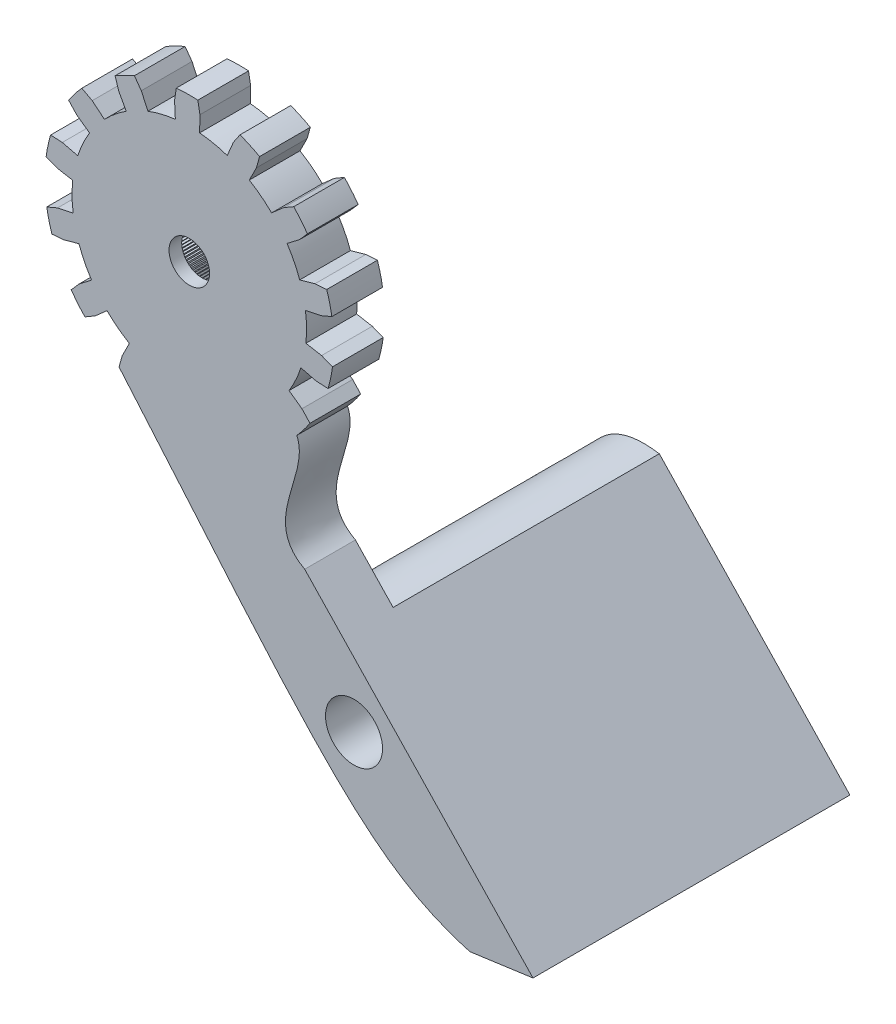
SolidWorks part; units mm, degrees
ref_plane "Front Plane" through (0, 0, 0) normal (0, 0, 1) x (1, 0, 0)
ref_plane "Top Plane" through (0, 0, 0) normal (0, 1, 0) x (1, 0, 0)
ref_plane "Right Plane" through (0, 0, 0) normal (1, 0, 0) x (0, 0, -1)
sketch "Sketch2" plane through (0, 0, 0) normal (0, 0, 1) x (1, 0, 0)
  line L0 (11.1946, 10) -> (11.1946, 10.6054) construction
  line L669 (17.6878, 7.31) -> (18.6279, 8.138)
  line L670 (18.6279, 8.138) -> (19.4304, 8.6044)
  line L671 (21.6272, -0.4657) -> (22.4922, -0.8024)
  line L672 (20.3937, -0.247) -> (21.6272, -0.4657)
  line L673 (20.3589, 1.9784) -> (21.5849, 2.2356)
  line L674 (21.5849, 2.2356) -> (22.439, 2.5991)
  line L675 (21.1094, 4.1784) -> (22.0348, 4.2505)
  line L676 (19.9032, 3.8403) -> (21.1094, 4.1784)
  line L677 (18.9062, 5.8303) -> (19.8993, 6.5939)
  line L678 (19.8993, 6.5939) -> (20.511, 7.292)
  line L679 (14.4587, -7.9329) -> (14.9822, -9.071)
  line L680 (14.9822, -9.071) -> (15.5266, -9.8227)
  line L681 (16.7705, -8.175) -> (17.0467, -9.0612)
  line L682 (16.1724, -7.0743) -> (16.7705, -8.175)
  line L683 (17.8907, -5.6595) -> (18.8561, -6.4578)
  line L684 (18.8561, -6.4578) -> (19.6729, -6.8988)
  line L685 (20.0786, -4.8746) -> (20.7119, -5.5532)
  line L686 (19.0622, -4.1424) -> (20.0786, -4.8746)
  line L687 (19.9964, -2.1222) -> (21.2126, -2.4225)
  line L688 (21.2126, -2.4225) -> (22.1398, -2.4655)
  line L689 (3.4829, -4.3861) -> (2.4899, -5.1497)
  line L690 (2.4899, -5.1497) -> (1.8781, -5.8478)
  line L691 (3.7613, -6.6939) -> (2.9588, -7.1603)
  line L692 (4.7013, -5.8658) -> (3.7613, -6.6939)
  line L693 (6.463, -7.2262) -> (5.8996, -8.3451)
  line L694 (5.8996, -8.3451) -> (5.6513, -9.2394)
  line L695 (7.7151, -9.1846) -> (7.1944, -9.953)
  line L696 (8.2027, -8.0307) -> (7.7151, -9.1846)
  line L697 (10.3802, -8.492) -> (10.3581, -9.7445)
  line L698 (10.3581, -9.7445) -> (10.5224, -10.6581)
  line L699 (12.358, -9.7133) -> (12.2223, -10.6315)
  line L700 (12.2967, -8.462) -> (12.358, -9.7133)
  line L701 (2.3105, 6.3188) -> (1.6772, 6.9974)
  line L702 (3.327, 5.5866) -> (2.3105, 6.3188)
  line L703 (2.3927, 3.5664) -> (1.1765, 3.8667)
  line L704 (1.1765, 3.8667) -> (0.2493, 3.9097)
  line L705 (0.762, 1.9099) -> (-0.103, 2.2465)
  line L706 (1.9955, 1.6912) -> (0.762, 1.9099)
  line L707 (2.0303, -0.5343) -> (0.8042, -0.7914)
  line L708 (0.8042, -0.7914) -> (-0.0498, -1.1549)
  line L709 (1.2798, -2.7343) -> (0.3543, -2.8063)
  line L710 (2.486, -2.3961) -> (1.2798, -2.7343)
  line L711 (12.009, 9.9362) -> (12.0311, 11.1887)
  line L712 (12.0311, 11.1887) -> (11.8667, 12.1023)
  line L713 (10.0311, 11.1574) -> (10.1668, 12.0757)
  line L714 (10.0924, 9.9062) -> (10.0311, 11.1574)
  line L715 (7.9305, 9.377) -> (7.4069, 10.5151)
  line L716 (7.4069, 10.5151) -> (6.8625, 11.2669)
  line L717 (5.6186, 9.6192) -> (5.3425, 10.5054)
  line L718 (6.2167, 8.5185) -> (5.6186, 9.6192)
  line L719 (4.4985, 7.1037) -> (3.533, 7.9019)
  line L720 (3.533, 7.9019) -> (2.7163, 8.343)
  line L721 (15.9262, 8.6703) -> (16.4895, 9.7892)
  line L722 (16.4895, 9.7892) -> (16.7378, 10.6836)
  line L723 (14.6741, 10.6288) -> (15.1948, 11.3972)
  line L724 (14.1864, 9.4749) -> (14.6741, 10.6288)
  arc A141 (20.511, 7.292) -> (19.4304, 8.6044) centre (11.1946, 0.7221) ccw
  arc A145 (17.6878, 7.31) -> (15.9262, 8.6703) centre (11.1946, 0.7221) ccw
  arc A149 (22.439, 2.5991) -> (22.0348, 4.2505) centre (11.1946, 0.7221) ccw
  arc A151 (22.1398, -2.4655) -> (22.4922, -0.8024) centre (11.1946, 0.7221) ccw
  arc A152 (19.6729, -6.8988) -> (20.7119, -5.5532) centre (11.1946, 0.7221) ccw
  arc A153 (15.5266, -9.8227) -> (17.0467, -9.0612) centre (11.1946, 0.7221) ccw
  arc A154 (10.5224, -10.6581) -> (12.2223, -10.6315) centre (11.1946, 0.7221) ccw
  arc A155 (5.6513, -9.2394) -> (7.1944, -9.953) centre (11.1946, 0.7221) ccw
  arc A156 (1.8781, -5.8478) -> (2.9588, -7.1603) centre (11.1946, 0.7221) ccw
  arc A157 (-0.0498, -1.1549) -> (0.3543, -2.8063) centre (11.1946, 0.7221) ccw
  arc A158 (0.2493, 3.9097) -> (-0.103, 2.2465) centre (11.1946, 0.7221) ccw
  arc A159 (2.7163, 8.343) -> (1.6772, 6.9974) centre (11.1946, 0.7221) ccw
  arc A160 (6.8625, 11.2669) -> (5.3425, 10.5054) centre (11.1946, 0.7221) ccw
  arc A161 (11.8667, 12.1023) -> (10.1668, 12.0757) centre (11.1946, 0.7221) ccw
  arc A162 (16.7378, 10.6836) -> (15.1948, 11.3972) centre (11.1946, 0.7221) ccw
  arc A163 (19.9032, 3.8403) -> (18.9062, 5.8303) centre (11.1946, 0.7221) ccw
  arc A164 (20.3937, -0.247) -> (20.3589, 1.9784) centre (11.1946, 0.7221) ccw
  arc A165 (19.0622, -4.1424) -> (19.9964, -2.1222) centre (11.1946, 0.7221) ccw
  arc A166 (16.1724, -7.0743) -> (17.8907, -5.6595) centre (11.1946, 0.7221) ccw
  arc A167 (12.2967, -8.462) -> (14.4587, -7.9329) centre (11.1946, 0.7221) ccw
  arc A168 (8.2027, -8.0307) -> (10.3802, -8.492) centre (11.1946, 0.7221) ccw
  arc A169 (4.7013, -5.8658) -> (6.463, -7.2262) centre (11.1946, 0.7221) ccw
  arc A170 (2.486, -2.3961) -> (3.4829, -4.3861) centre (11.1946, 0.7221) ccw
  arc A171 (1.9955, 1.6912) -> (2.0303, -0.5343) centre (11.1946, 0.7221) ccw
  arc A172 (3.327, 5.5866) -> (2.3927, 3.5664) centre (11.1946, 0.7221) ccw
  arc A173 (6.2167, 8.5185) -> (4.4985, 7.1037) centre (11.1946, 0.7221) ccw
  arc A174 (10.0924, 9.9062) -> (7.9305, 9.377) centre (11.1946, 0.7221) ccw
  arc A175 (14.1864, 9.4749) -> (12.009, 9.9362) centre (11.1946, 0.7221) ccw
extrude "Boss-Extrude1" add sketch "Sketch2" against normal blind 4
sketch "Sketch3" plane through (0, 0, 0) normal (0, 0, 1) x (1, 0, 0)
  circle A0 centre (11.3203, 0.7378) radius 3.5
  point P2 (11.3203, 0.7378)
  dimension "D1" = 7
extrude "Boss-Extrude2" add sketch "Sketch3" against normal blind 1
sketch "Sketch4" plane through (0, 0, 0) normal (0, 0, 1) x (1, 0, 0)
  circle A0 centre (11.1946, 0.7221) radius 4.295 construction
sketch "Sketch5" plane through (0, 0, 0) normal (0, 0, 1) x (1, 0, 0)
  line L0 (10.0276, -11.444) -> (15.4878, -11.444) construction
  line L1 (4.4176, 11.5) -> (18.1778, 11.5) construction
  line L5 (20.2959, -15.7283) -> (38.3061, -34.6532)
  line L7 (33.3336, -35.343) -> (38.3061, -34.6532)
  line L25 (15.9262, 8.6703) -> (16.4895, 9.7892)
  line L35 (3.4829, -4.3861) -> (2.4899, -5.1497)
  line L45 (15.1948, 11.3972) -> (14.6741, 10.6288)
  line L55 (14.6741, 10.6288) -> (14.1864, 9.4749)
  line L98 (22.0348, 4.2505) -> (21.1094, 4.1784)
  line L102 (12.009, 9.9362) -> (12.0311, 11.1887)
  line L104 (14.9822, -9.071) -> (15.5266, -9.8227)
  line L105 (14.9822, -9.071) -> (15.5266, -9.8227)
  line L110 (2.4899, -5.1497) -> (1.8781, -5.8478)
  line L114 (5.8996, -8.3451) -> (5.6513, -9.2394)
  line L124 (2.3927, 3.5664) -> (1.1765, 3.8667)
  line L126 (1.1765, 3.8667) -> (0.2493, 3.9097)
  line L130 (0.8042, -0.7914) -> (-0.0498, -1.1549)
  line L140 (5.3425, 10.5054) -> (5.6186, 9.6192)
  line L146 (16.4895, 9.7892) -> (16.7378, 10.6836)
  line L153 (12.0311, 11.1887) -> (11.8667, 12.1023)
  line L157 (10.1668, 12.0757) -> (10.0311, 11.1574)
  line L161 (10.0311, 11.1574) -> (10.0924, 9.9062)
  line L196 (7.9305, 9.377) -> (7.4069, 10.5151)
  line L198 (7.4069, 10.5151) -> (6.8625, 11.2669)
  line L200 (5.6186, 9.6192) -> (6.2167, 8.5185)
  line L202 (4.4985, 7.1037) -> (3.533, 7.9019)
  line L204 (3.533, 7.9019) -> (2.7163, 8.343)
  line L206 (1.6772, 6.9974) -> (2.3105, 6.3188)
  line L208 (2.3105, 6.3188) -> (3.327, 5.5866)
  line L210 (-0.103, 2.2465) -> (0.762, 1.9099)
  line L212 (0.762, 1.9099) -> (1.9955, 1.6912)
  line L214 (2.0303, -0.5343) -> (0.8042, -0.7914)
  line L216 (0.3543, -2.8063) -> (1.2798, -2.7343)
  line L218 (1.2798, -2.7343) -> (2.486, -2.3961)
  line L220 (2.9588, -7.1603) -> (3.7613, -6.6939)
  line L222 (3.7613, -6.6939) -> (4.7013, -5.8658)
  line L224 (6.463, -7.2262) -> (5.8996, -8.3451)
  line L226 (7.1944, -9.953) -> (7.7151, -9.1846)
  line L227 (7.1944, -9.953) -> (7.7151, -9.1846)
  line L228 (7.7151, -9.1846) -> (8.2027, -8.0307)
  line L229 (7.7151, -9.1846) -> (8.2027, -8.0307)
  line L230 (10.3802, -8.492) -> (10.3581, -9.7445)
  line L231 (10.3802, -8.492) -> (10.3581, -9.7445)
  line L232 (10.3581, -9.7445) -> (10.5224, -10.6581)
  line L233 (10.3581, -9.7445) -> (10.5224, -10.6581)
  line L234 (12.2223, -10.6315) -> (12.358, -9.7133)
  line L235 (12.2223, -10.6315) -> (12.358, -9.7133)
  line L236 (12.358, -9.7133) -> (12.2967, -8.462)
  line L237 (12.358, -9.7133) -> (12.2967, -8.462)
  line L238 (14.4587, -7.9329) -> (14.9822, -9.071)
  line L239 (14.4587, -7.9329) -> (14.9822, -9.071)
  line L240 (17.0467, -9.0612) -> (16.7705, -8.175)
  line L241 (17.0467, -9.0612) -> (16.7705, -8.175)
  line L242 (16.7705, -8.175) -> (16.1724, -7.0743)
  line L243 (16.7705, -8.175) -> (16.1724, -7.0743)
  line L244 (17.8907, -5.6595) -> (18.8561, -6.4578)
  line L245 (17.8907, -5.6595) -> (18.8561, -6.4578)
  line L246 (18.8561, -6.4578) -> (19.6729, -6.8988)
  line L247 (18.8561, -6.4578) -> (19.6729, -6.8988)
  line L248 (20.7119, -5.5532) -> (20.0786, -4.8746)
  line L250 (20.0786, -4.8746) -> (19.0622, -4.1424)
  line L252 (19.9964, -2.1222) -> (21.2126, -2.4225)
  line L254 (21.2126, -2.4225) -> (22.1398, -2.4655)
  line L256 (22.4922, -0.8024) -> (21.6272, -0.4657)
  line L258 (21.6272, -0.4657) -> (20.3937, -0.247)
  line L260 (20.3589, 1.9784) -> (21.5849, 2.2356)
  line L262 (21.5849, 2.2356) -> (22.439, 2.5991)
  line L264 (21.1094, 4.1784) -> (19.9032, 3.8403)
  line L266 (18.9062, 5.8303) -> (19.8993, 6.5939)
  line L268 (19.8993, 6.5939) -> (20.511, 7.292)
  line L270 (19.4304, 8.6044) -> (18.6279, 8.138)
  line L272 (18.6279, 8.138) -> (17.6878, 7.31)
  arc A14 (17.6878, 7.31) -> (15.9262, 8.6703) centre (11.1946, 0.7221) ccw
  arc A36 (16.7378, 10.6836) -> (15.1948, 11.3972) centre (11.1946, 0.7221) ccw
  arc A44 (14.1864, 9.4749) -> (12.009, 9.9362) centre (11.1946, 0.7221) ccw
  arc A52 (11.8667, 12.1023) -> (10.1668, 12.0757) centre (11.1946, 0.7221) ccw
  arc A98 (10.0924, 9.9062) -> (7.9305, 9.377) centre (11.1946, 0.7221) ccw
  arc A100 (6.8625, 11.2669) -> (5.3425, 10.5054) centre (11.1946, 0.7221) ccw
  arc A102 (6.2167, 8.5185) -> (4.4985, 7.1037) centre (11.1946, 0.7221) ccw
  arc A104 (2.7163, 8.343) -> (1.6772, 6.9974) centre (11.1946, 0.7221) ccw
  arc A106 (3.327, 5.5866) -> (2.3927, 3.5664) centre (11.1946, 0.7221) ccw
  arc A108 (0.2493, 3.9097) -> (-0.103, 2.2465) centre (11.1946, 0.7221) ccw
  arc A110 (1.9955, 1.6912) -> (2.0303, -0.5343) centre (11.1946, 0.7221) ccw
  arc A112 (-0.0498, -1.1549) -> (0.3543, -2.8063) centre (11.1946, 0.7221) ccw
  arc A114 (2.486, -2.3961) -> (3.4829, -4.3861) centre (11.1946, 0.7221) ccw
  arc A116 (1.8781, -5.8478) -> (2.9588, -7.1603) centre (11.1946, 0.7221) ccw
  arc A118 (4.7013, -5.8658) -> (6.463, -7.2262) centre (11.1946, 0.7221) ccw
  arc A120 (5.6513, -9.2394) -> (7.1944, -9.953) centre (11.1946, 0.7221) ccw
  arc A121 (5.6513, -9.2394) -> (7.1944, -9.953) centre (11.1946, 0.7221) ccw
  arc A122 (8.2027, -8.0307) -> (10.3802, -8.492) centre (11.1946, 0.7221) ccw
  arc A123 (8.2027, -8.0307) -> (10.3802, -8.492) centre (11.1946, 0.7221) ccw
  arc A124 (10.5224, -10.6581) -> (12.2223, -10.6315) centre (11.1946, 0.7221) ccw
  arc A125 (10.5224, -10.6581) -> (12.2223, -10.6315) centre (11.1946, 0.7221) ccw
  arc A126 (12.2967, -8.462) -> (14.4587, -7.9329) centre (11.1946, 0.7221) ccw
  arc A127 (12.2967, -8.462) -> (14.4587, -7.9329) centre (11.1946, 0.7221) ccw
  arc A128 (15.5266, -9.8227) -> (17.0467, -9.0612) centre (11.1946, 0.7221) ccw
  arc A129 (15.5266, -9.8227) -> (17.0467, -9.0612) centre (11.1946, 0.7221) ccw
  arc A130 (16.1724, -7.0743) -> (17.8907, -5.6595) centre (11.1946, 0.7221) ccw
  arc A131 (16.1724, -7.0743) -> (17.8907, -5.6595) centre (11.1946, 0.7221) ccw
  arc A132 (19.6729, -6.8988) -> (20.7119, -5.5532) centre (11.1946, 0.7221) ccw
  arc A134 (19.0622, -4.1424) -> (19.9964, -2.1222) centre (11.1946, 0.7221) ccw
  arc A136 (22.1398, -2.4655) -> (22.4922, -0.8024) centre (11.1946, 0.7221) ccw
  arc A138 (20.3937, -0.247) -> (20.3589, 1.9784) centre (11.1946, 0.7221) ccw
  arc A140 (22.439, 2.5991) -> (22.0348, 4.2505) centre (11.1946, 0.7221) ccw
  arc A142 (19.9032, 3.8403) -> (18.9062, 5.8303) centre (11.1946, 0.7221) ccw
  arc A144 (20.511, 7.292) -> (19.4304, 8.6044) centre (11.1946, 0.7221) ccw
  spline S0 degree 3 poles (19.6729, -6.8988) (20.7965, -9.2961) (16.694, -13.7781) (20.2959, -15.7283) knots 0 0 0 0 1 1 1 1
  spline S1 degree 3 poles (33.3336, -35.343) (25.4692, -33.1533) (21.4591, -27.7657) (5.6513, -9.2394) knots 0.222416 0.222416 0.222416 0.222416 1 1 1 1
  dimension "D1" = 0
extrude "Boss-Extrude3" add sketch "Sketch5" against normal up to surface (4 mm away) up to face at (11.1946, 0.7221, -4)
sketch "Sketch6" plane through (0, 0, -4) normal (0, 0, -1) x (-1, 0, 0)
  line L1 (-38.3061, -34.6532) -> (-20.2959, -15.7283) construction
  line L2 (-38.3061, -34.6532) -> (-23.2711, -18.8546)
  line L24 (-2.4899, -5.1497) -> (-3.4829, -4.3861)
  line L32 (-20.2959, -15.7283) -> (-38.3061, -34.6532)
  line L86 (-38.3061, -34.6532) -> (-33.3336, -35.343)
  line L88 (-38.3061, -34.6532) -> (-33.3336, -35.343)
  line L141 (-16.7378, 10.6836) -> (-16.4895, 9.7892)
  line L147 (-5.6186, 9.6192) -> (-5.3425, 10.5054)
  line L157 (0.0498, -1.1549) -> (-0.8042, -0.7914)
  line L161 (-0.2493, 3.9097) -> (-1.1765, 3.8667)
  line L163 (-1.1765, 3.8667) -> (-2.3927, 3.5664)
  line L173 (-5.6513, -9.2394) -> (-5.8996, -8.3451)
  line L177 (-1.8781, -5.8478) -> (-2.4899, -5.1497)
  line L206 (-21.1094, 4.1784) -> (-22.0348, 4.2505)
  line L208 (-17.6878, 7.31) -> (-18.6279, 8.138)
  line L210 (-18.6279, 8.138) -> (-19.4304, 8.6044)
  line L212 (-20.511, 7.292) -> (-19.8993, 6.5939)
  line L214 (-19.8993, 6.5939) -> (-18.9062, 5.8303)
  line L216 (-19.9032, 3.8403) -> (-21.1094, 4.1784)
  line L218 (-22.439, 2.5991) -> (-21.5849, 2.2356)
  line L220 (-21.5849, 2.2356) -> (-20.3589, 1.9784)
  line L222 (-20.3937, -0.247) -> (-21.6272, -0.4657)
  line L224 (-21.6272, -0.4657) -> (-22.4922, -0.8024)
  line L226 (-22.1398, -2.4655) -> (-21.2126, -2.4225)
  line L228 (-21.2126, -2.4225) -> (-19.9964, -2.1222)
  line L230 (-19.0622, -4.1424) -> (-20.0786, -4.8746)
  line L232 (-20.0786, -4.8746) -> (-20.7119, -5.5532)
  line L256 (-5.8996, -8.3451) -> (-6.463, -7.2262)
  line L258 (-4.7013, -5.8658) -> (-3.7613, -6.6939)
  line L260 (-3.7613, -6.6939) -> (-2.9588, -7.1603)
  line L262 (-2.486, -2.3961) -> (-1.2798, -2.7343)
  line L264 (-1.2798, -2.7343) -> (-0.3543, -2.8063)
  line L266 (-0.8042, -0.7914) -> (-2.0303, -0.5343)
  line L268 (-1.9955, 1.6912) -> (-0.762, 1.9099)
  line L270 (-0.762, 1.9099) -> (0.103, 2.2465)
  line L272 (-3.327, 5.5866) -> (-2.3105, 6.3188)
  line L274 (-2.3105, 6.3188) -> (-1.6772, 6.9974)
  line L276 (-2.7163, 8.343) -> (-3.533, 7.9019)
  line L278 (-3.533, 7.9019) -> (-4.4985, 7.1037)
  line L280 (-6.2167, 8.5185) -> (-5.6186, 9.6192)
  line L282 (-6.8625, 11.2669) -> (-7.4069, 10.5151)
  line L284 (-7.4069, 10.5151) -> (-7.9305, 9.377)
  line L286 (-10.0924, 9.9062) -> (-10.0311, 11.1574)
  line L288 (-10.0311, 11.1574) -> (-10.1668, 12.0757)
  line L290 (-11.8667, 12.1023) -> (-12.0311, 11.1887)
  line L292 (-12.0311, 11.1887) -> (-12.009, 9.9362)
  line L294 (-14.1864, 9.4749) -> (-14.6741, 10.6288)
  line L296 (-14.6741, 10.6288) -> (-15.1948, 11.3972)
  line L298 (-16.4895, 9.7892) -> (-15.9262, 8.6703)
  arc A44 (-15.9262, 8.6703) -> (-17.6878, 7.31) centre (-11.1946, 0.7221) ccw
  arc A85 (-19.4304, 8.6044) -> (-20.511, 7.292) centre (-11.1946, 0.7221) ccw
  arc A87 (-18.9062, 5.8303) -> (-19.9032, 3.8403) centre (-11.1946, 0.7221) ccw
  arc A89 (-22.0348, 4.2505) -> (-22.439, 2.5991) centre (-11.1946, 0.7221) ccw
  arc A91 (-20.3589, 1.9784) -> (-20.3937, -0.247) centre (-11.1946, 0.7221) ccw
  arc A93 (-22.4922, -0.8024) -> (-22.1398, -2.4655) centre (-11.1946, 0.7221) ccw
  arc A95 (-19.9964, -2.1222) -> (-19.0622, -4.1424) centre (-11.1946, 0.7221) ccw
  arc A97 (-20.7119, -5.5532) -> (-19.6729, -6.8988) centre (-11.1946, 0.7221) ccw
  arc A111 (-6.463, -7.2262) -> (-4.7013, -5.8658) centre (-11.1946, 0.7221) ccw
  arc A113 (-2.9588, -7.1603) -> (-1.8781, -5.8478) centre (-11.1946, 0.7221) ccw
  arc A115 (-3.4829, -4.3861) -> (-2.486, -2.3961) centre (-11.1946, 0.7221) ccw
  arc A117 (-0.3543, -2.8063) -> (0.0498, -1.1549) centre (-11.1946, 0.7221) ccw
  arc A119 (-2.0303, -0.5343) -> (-1.9955, 1.6912) centre (-11.1946, 0.7221) ccw
  arc A121 (0.103, 2.2465) -> (-0.2493, 3.9097) centre (-11.1946, 0.7221) ccw
  arc A123 (-2.3927, 3.5664) -> (-3.327, 5.5866) centre (-11.1946, 0.7221) ccw
  arc A125 (-1.6772, 6.9974) -> (-2.7163, 8.343) centre (-11.1946, 0.7221) ccw
  arc A127 (-4.4985, 7.1037) -> (-6.2167, 8.5185) centre (-11.1946, 0.7221) ccw
  arc A129 (-5.3425, 10.5054) -> (-6.8625, 11.2669) centre (-11.1946, 0.7221) ccw
  arc A131 (-7.9305, 9.377) -> (-10.0924, 9.9062) centre (-11.1946, 0.7221) ccw
  arc A133 (-10.1668, 12.0757) -> (-11.8667, 12.1023) centre (-11.1946, 0.7221) ccw
  arc A135 (-12.009, 9.9362) -> (-14.1864, 9.4749) centre (-11.1946, 0.7221) ccw
  arc A137 (-15.1948, 11.3972) -> (-16.7378, 10.6836) centre (-11.1946, 0.7221) ccw
  spline S1 degree 3 poles (1512.6013, 1291.381) (-1539.1869, -1123.2356) (1576.8428, 871.4346) (-1874.1777, -812.6257) knots -2.707308 -2.707308 -2.707308 -2.707308 4.551924 4.551924 4.551924 4.551924 only from (-5.6513, -9.2394) to (-33.3336, -35.343) construction
  spline S3 degree 3 poles (-17.1172, -22.6359) (-24.2126, -30.7109) (-27.8289, -33.8103) (-33.3336, -35.343) knots 0.455733 0.455733 0.455733 0.455733 1 1 1 1
  spline S4 degree 2 poles (-17.1172, -22.6359) (-18.6565, -18.1405) (-23.2711, -18.8546) knots 0 0 0 1 1 1
  spline S6 degree 3 poles (928.9961, -323.1558) (-986.7592, 351.2189) (950.6356, -365.5096) (-975.1186, 281.4128) knots -3.799895 -3.799895 -3.799895 -3.799895 4.619147 4.619147 4.619147 4.619147 only from (-19.6729, -6.8988) to (-20.2959, -15.7283)
  spline S7 degree 3 poles (-969.9828, -385.6106) (744.6842, 387.8248) (-748.6875, -572.1614) (734.9995, 662.636) knots -2.545715 -2.545715 -2.545715 -2.545715 3.160411 3.160411 3.160411 3.160411 only from (-33.3336, -35.343) to (-5.6513, -9.2394)
  dimension "D1" = 0
extrude "Boss-Extrude4" add sketch "Sketch6" along normal blind 21
sketch "Sketch7" plane through (0, 0, -4) normal (0, 0, -1) x (-1, 0, 0)
  line L200 (-9.7843, 3.3038) -> (-9.9297, 3.2201)
  line L201 (-9.7763, 3.1362) -> (-9.7843, 3.3038)
  line L202 (-9.6259, 3.2107) -> (-9.7763, 3.1362)
  line L203 (-9.6285, 3.0429) -> (-9.6259, 3.2107)
  line L204 (-9.4737, 3.1077) -> (-9.6285, 3.0429)
  line L205 (-9.4868, 2.9405) -> (-9.4737, 3.1077)
  line L206 (-9.3283, 2.9955) -> (-9.4868, 2.9405)
  line L207 (-9.3518, 2.8293) -> (-9.3283, 2.9955)
  line L208 (-9.1901, 2.8743) -> (-9.3518, 2.8293)
  line L209 (-9.2241, 2.7099) -> (-9.1901, 2.8743)
  line L210 (-9.0599, 2.7446) -> (-9.2241, 2.7099)
  line L211 (-9.1041, 2.5828) -> (-9.0599, 2.7446)
  line L212 (-8.9381, 2.6071) -> (-9.1041, 2.5828)
  line L213 (-8.9923, 2.4483) -> (-8.9381, 2.6071)
  line L214 (-8.8251, 2.4622) -> (-8.9923, 2.4483)
  line L215 (-8.8892, 2.3071) -> (-8.8251, 2.4622)
  line L216 (-8.7215, 2.3104) -> (-8.8892, 2.3071)
  line L217 (-8.7952, 2.1597) -> (-8.7215, 2.3104)
  line L218 (-8.6276, 2.1525) -> (-8.7952, 2.1597)
  line L219 (-8.7106, 2.0067) -> (-8.6276, 2.1525)
  line L220 (-8.5438, 1.9889) -> (-8.7106, 2.0067)
  line L221 (-8.6358, 1.8487) -> (-8.5438, 1.9889)
  line L222 (-8.4704, 1.8205) -> (-8.6358, 1.8487)
  line L223 (-8.571, 1.6862) -> (-8.4704, 1.8205)
  line L224 (-8.4077, 1.6477) -> (-8.571, 1.6862)
  line L225 (-8.5166, 1.5201) -> (-8.4077, 1.6477)
  line L226 (-8.3561, 1.4714) -> (-8.5166, 1.5201)
  line L227 (-8.4727, 1.3508) -> (-8.3561, 1.4714)
  line L228 (-8.3156, 1.2922) -> (-8.4727, 1.3508)
  line L229 (-8.4396, 1.1792) -> (-8.3156, 1.2922)
  line L230 (-8.2864, 1.1108) -> (-8.4396, 1.1792)
  line L231 (-8.4173, 1.0058) -> (-8.2864, 1.1108)
  line L232 (-8.2687, 0.9279) -> (-8.4173, 1.0058)
  line L233 (-8.4059, 0.8313) -> (-8.2687, 0.9279)
  line L234 (-8.2625, 0.7442) -> (-8.4059, 0.8313)
  line L235 (-8.4055, 0.6565) -> (-8.2625, 0.7442)
  line L236 (-8.2678, 0.5605) -> (-8.4055, 0.6565)
  line L237 (-8.416, 0.4819) -> (-8.2678, 0.5605)
  line L238 (-8.2847, 0.3776) -> (-8.416, 0.4819)
  line L239 (-8.4375, 0.3084) -> (-8.2847, 0.3776)
  line L240 (-8.313, 0.196) -> (-8.4375, 0.3084)
  line L241 (-8.4699, 0.1366) -> (-8.313, 0.196)
  line L242 (-8.3527, 0.0166) -> (-8.4699, 0.1366)
  line L243 (-8.513, -0.0328) -> (-8.3527, 0.0166)
  line L244 (-8.4035, -0.16) -> (-8.513, -0.0328)
  line L245 (-8.5666, -0.1993) -> (-8.4035, -0.16)
  line L246 (-8.4653, -0.333) -> (-8.5666, -0.1993)
  line L247 (-8.6306, -0.362) -> (-8.4653, -0.333)
  line L248 (-8.5379, -0.5018) -> (-8.6306, -0.362)
  line L249 (-8.7047, -0.5203) -> (-8.5379, -0.5018)
  line L250 (-8.621, -0.6657) -> (-8.7047, -0.5203)
  line L251 (-8.7886, -0.6738) -> (-8.621, -0.6657)
  line L252 (-8.7141, -0.8241) -> (-8.7886, -0.6738)
  line L253 (-8.8819, -0.8216) -> (-8.7141, -0.8241)
  line L254 (-8.8171, -0.9763) -> (-8.8819, -0.8216)
  line L255 (-8.9843, -0.9633) -> (-8.8171, -0.9763)
  line L256 (-8.9293, -1.1218) -> (-8.9843, -0.9633)
  line L257 (-9.0955, -1.0983) -> (-8.9293, -1.1218)
  line L258 (-9.0505, -1.2599) -> (-9.0955, -1.0983)
  line L259 (-9.2148, -1.226) -> (-9.0505, -1.2599)
  line L260 (-9.1802, -1.3901) -> (-9.2148, -1.226)
  line L261 (-9.342, -1.346) -> (-9.1802, -1.3901)
  line L262 (-9.3177, -1.512) -> (-9.342, -1.346)
  line L263 (-9.4765, -1.4577) -> (-9.3177, -1.512)
  line L264 (-9.4626, -1.6249) -> (-9.4765, -1.4577)
  line L265 (-9.6177, -1.5608) -> (-9.4626, -1.6249)
  line L266 (-9.6144, -1.7286) -> (-9.6177, -1.5608)
  line L267 (-9.7651, -1.6549) -> (-9.6144, -1.7286)
  line L268 (-9.7723, -1.8225) -> (-9.7651, -1.6549)
  line L269 (-9.9181, -1.7395) -> (-9.7723, -1.8225)
  line L270 (-9.9358, -1.9063) -> (-9.9181, -1.7395)
  line L271 (-10.0761, -1.8143) -> (-9.9358, -1.9063)
  line L272 (-10.1043, -1.9797) -> (-10.0761, -1.8143)
  line L273 (-10.2385, -1.879) -> (-10.1043, -1.9797)
  line L274 (-10.2771, -2.0423) -> (-10.2385, -1.879)
  line L275 (-10.4047, -1.9334) -> (-10.2771, -2.0423)
  line L276 (-10.4534, -2.094) -> (-10.4047, -1.9334)
  line L277 (-10.5739, -1.9773) -> (-10.4534, -2.094)
  line L278 (-10.6326, -2.1345) -> (-10.5739, -1.9773)
  line L279 (-10.7456, -2.0105) -> (-10.6326, -2.1345)
  line L280 (-10.814, -2.1637) -> (-10.7456, -2.0105)
  line L281 (-10.919, -2.0328) -> (-10.814, -2.1637)
  line L282 (-10.9969, -2.1814) -> (-10.919, -2.0328)
  line L283 (-11.0935, -2.0442) -> (-10.9969, -2.1814)
  line L284 (-11.1806, -2.1876) -> (-11.0935, -2.0442)
  line L285 (-11.2683, -2.0446) -> (-11.1806, -2.1876)
  line L286 (-11.3643, -2.1822) -> (-11.2683, -2.0446)
  line L287 (-11.4429, -2.034) -> (-11.3643, -2.1822)
  line L288 (-11.5472, -2.1654) -> (-11.4429, -2.034)
  line L289 (-11.6164, -2.0125) -> (-11.5472, -2.1654)
  line L290 (-11.7288, -2.1371) -> (-11.6164, -2.0125)
  line L291 (-11.7882, -1.9802) -> (-11.7288, -2.1371)
  line L292 (-11.9082, -2.0974) -> (-11.7882, -1.9802)
  line L293 (-11.9576, -1.9371) -> (-11.9082, -2.0974)
  line L294 (-12.0848, -2.0465) -> (-11.9576, -1.9371)
  line L295 (-12.1241, -1.8834) -> (-12.0848, -2.0465)
  line L296 (-12.2578, -1.9847) -> (-12.1241, -1.8834)
  line L297 (-12.2868, -1.8194) -> (-12.2578, -1.9847)
  line L298 (-12.4266, -1.9121) -> (-12.2868, -1.8194)
  line L299 (-12.4451, -1.7454) -> (-12.4266, -1.9121)
  line L300 (-12.5905, -1.8291) -> (-12.4451, -1.7454)
  line L301 (-12.5985, -1.6615) -> (-12.5905, -1.8291)
  line L302 (-12.7489, -1.7359) -> (-12.5985, -1.6615)
  line L303 (-12.7464, -1.5682) -> (-12.7489, -1.7359)
  line L304 (-12.9011, -1.633) -> (-12.7464, -1.5682)
  line L305 (-12.8881, -1.4657) -> (-12.9011, -1.633)
  line L306 (-13.0466, -1.5207) -> (-12.8881, -1.4657)
  line L307 (-13.0231, -1.3546) -> (-13.0466, -1.5207)
  line L308 (-13.1847, -1.3995) -> (-13.0231, -1.3546)
  line L309 (-13.1508, -1.2352) -> (-13.1847, -1.3995)
  line L310 (-13.3149, -1.2699) -> (-13.1508, -1.2352)
  line L311 (-13.2708, -1.108) -> (-13.3149, -1.2699)
  line L312 (-13.4368, -1.1323) -> (-13.2708, -1.108)
  line L313 (-13.3825, -0.9736) -> (-13.4368, -1.1323)
  line L314 (-13.5497, -0.9874) -> (-13.3825, -0.9736)
  line L315 (-13.4856, -0.8324) -> (-13.5497, -0.9874)
  line L316 (-13.6534, -0.8357) -> (-13.4856, -0.8324)
  line L317 (-13.5797, -0.685) -> (-13.6534, -0.8357)
  line L318 (-13.7473, -0.6777) -> (-13.5797, -0.685)
  line L319 (-13.6643, -0.5319) -> (-13.7473, -0.6777)
  line L320 (-13.8311, -0.5142) -> (-13.6643, -0.5319)
  line L321 (-13.7391, -0.3739) -> (-13.8311, -0.5142)
  line L322 (-13.9045, -0.3457) -> (-13.7391, -0.3739)
  line L323 (-13.8038, -0.2115) -> (-13.9045, -0.3457)
  line L324 (-13.9671, -0.173) -> (-13.8038, -0.2115)
  line L325 (-13.8582, -0.0453) -> (-13.9671, -0.173)
  line L326 (-14.0188, 0.0033) -> (-13.8582, -0.0453)
  line L327 (-13.9021, 0.1239) -> (-14.0188, 0.0033)
  line L328 (-14.0593, 0.1826) -> (-13.9021, 0.1239)
  line L329 (-13.9353, 0.2956) -> (-14.0593, 0.1826)
  line L330 (-14.0885, 0.364) -> (-13.9353, 0.2956)
  line L331 (-13.9576, 0.469) -> (-14.0885, 0.364)
  line L332 (-14.1062, 0.5469) -> (-13.9576, 0.469)
  line L333 (-13.969, 0.6434) -> (-14.1062, 0.5469)
  line L334 (-14.1124, 0.7305) -> (-13.969, 0.6434)
  line L335 (-13.9694, 0.8183) -> (-14.1124, 0.7305)
  line L336 (-14.107, 0.9142) -> (-13.9694, 0.8183)
  line L337 (-13.9588, 0.9928) -> (-14.107, 0.9142)
  line L338 (-14.0902, 1.0972) -> (-13.9588, 0.9928)
  line L339 (-13.9373, 1.1663) -> (-14.0902, 1.0972)
  line L340 (-14.0619, 1.2787) -> (-13.9373, 1.1663)
  line L341 (-13.9049, 1.3381) -> (-14.0619, 1.2787)
  line L342 (-14.0222, 1.4582) -> (-13.9049, 1.3381)
  line L343 (-13.8619, 1.5076) -> (-14.0222, 1.4582)
  line L344 (-13.9713, 1.6347) -> (-13.8619, 1.5076)
  line L345 (-13.8082, 1.674) -> (-13.9713, 1.6347)
  line L346 (-13.9095, 1.8078) -> (-13.8082, 1.674)
  line L347 (-13.7442, 1.8367) -> (-13.9095, 1.8078)
  line L348 (-13.8369, 1.9766) -> (-13.7442, 1.8367)
  line L349 (-13.6702, 1.9951) -> (-13.8369, 1.9766)
  line L350 (-13.7539, 2.1405) -> (-13.6702, 1.9951)
  line L351 (-13.5863, 2.1485) -> (-13.7539, 2.1405)
  line L352 (-13.6607, 2.2989) -> (-13.5863, 2.1485)
  line L353 (-13.493, 2.2963) -> (-13.6607, 2.2989)
  line L354 (-13.5578, 2.4511) -> (-13.493, 2.2963)
  line L355 (-13.3905, 2.438) -> (-13.5578, 2.4511)
  line L356 (-13.4455, 2.5965) -> (-13.3905, 2.438)
  line L357 (-13.2794, 2.573) -> (-13.4455, 2.5965)
  line L358 (-13.3243, 2.7347) -> (-13.2794, 2.573)
  line L359 (-13.16, 2.7007) -> (-13.3243, 2.7347)
  line L360 (-13.1947, 2.8649) -> (-13.16, 2.7007)
  line L361 (-13.0328, 2.8207) -> (-13.1947, 2.8649)
  line L362 (-13.0571, 2.9867) -> (-13.0328, 2.8207)
  line L363 (-12.8984, 2.9325) -> (-13.0571, 2.9867)
  line L364 (-12.9122, 3.0997) -> (-12.8984, 2.9325)
  line L365 (-12.7572, 3.0356) -> (-12.9122, 3.0997)
  line L366 (-12.7605, 3.2033) -> (-12.7572, 3.0356)
  line L367 (-12.6098, 3.1296) -> (-12.7605, 3.2033)
  line L368 (-12.6025, 3.2972) -> (-12.6098, 3.1296)
  line L369 (-12.4567, 3.2142) -> (-12.6025, 3.2972)
  line L370 (-12.439, 3.381) -> (-12.4567, 3.2142)
  line L371 (-12.2987, 3.289) -> (-12.439, 3.381)
  line L372 (-12.2705, 3.4544) -> (-12.2987, 3.289)
  line L373 (-12.1363, 3.3538) -> (-12.2705, 3.4544)
  line L374 (-12.0978, 3.5171) -> (-12.1363, 3.3538)
  line L375 (-11.9701, 3.4082) -> (-12.0978, 3.5171)
  line L376 (-11.9215, 3.5687) -> (-11.9701, 3.4082)
  line L377 (-11.8009, 3.4521) -> (-11.9215, 3.5687)
  line L378 (-11.7422, 3.6092) -> (-11.8009, 3.4521)
  line L379 (-11.6292, 3.4852) -> (-11.7422, 3.6092)
  line L380 (-11.5608, 3.6384) -> (-11.6292, 3.4852)
  line L381 (-11.4558, 3.5075) -> (-11.5608, 3.6384)
  line L382 (-11.3779, 3.6561) -> (-11.4558, 3.5075)
  line L383 (-11.2814, 3.5189) -> (-11.3779, 3.6561)
  line L384 (-11.1943, 3.6623) -> (-11.2814, 3.5189)
  line L385 (-11.1065, 3.5193) -> (-11.1943, 3.6623)
  line L386 (-11.0106, 3.657) -> (-11.1065, 3.5193)
  line L387 (-10.932, 3.5088) -> (-11.0106, 3.657)
  line L388 (-10.8276, 3.6401) -> (-10.932, 3.5088)
  line L389 (-10.7585, 3.4873) -> (-10.8276, 3.6401)
  line L390 (-10.6461, 3.6118) -> (-10.7585, 3.4873)
  line L391 (-10.5867, 3.4549) -> (-10.6461, 3.6118)
  line L392 (-10.4666, 3.5721) -> (-10.5867, 3.4549)
  line L393 (-10.4172, 3.4118) -> (-10.4666, 3.5721)
  line L394 (-10.2901, 3.5213) -> (-10.4172, 3.4118)
  line L395 (-10.2508, 3.3582) -> (-10.2901, 3.5213)
  line L396 (-10.117, 3.4594) -> (-10.2508, 3.3582)
  line L397 (-10.0881, 3.2942) -> (-10.117, 3.4594)
  line L398 (-9.9482, 3.3869) -> (-10.0881, 3.2942)
  line L399 (-9.9297, 3.2201) -> (-9.9482, 3.3869)
  line L400 (-9.7843, 3.3038) -> (-9.9297, 3.2201)
  line L401 (-9.7763, 3.1362) -> (-9.7843, 3.3038)
  line L402 (-9.6259, 3.2107) -> (-9.7763, 3.1362)
  line L403 (-9.6285, 3.0429) -> (-9.6259, 3.2107)
  line L404 (-9.4737, 3.1077) -> (-9.6285, 3.0429)
  line L405 (-9.4868, 2.9405) -> (-9.4737, 3.1077)
  line L406 (-9.3283, 2.9955) -> (-9.4868, 2.9405)
  line L407 (-9.3518, 2.8293) -> (-9.3283, 2.9955)
  line L408 (-9.1901, 2.8743) -> (-9.3518, 2.8293)
  line L409 (-9.2241, 2.7099) -> (-9.1901, 2.8743)
  line L410 (-9.0599, 2.7446) -> (-9.2241, 2.7099)
  line L411 (-9.1041, 2.5828) -> (-9.0599, 2.7446)
  line L412 (-8.9381, 2.6071) -> (-9.1041, 2.5828)
  line L413 (-8.9923, 2.4483) -> (-8.9381, 2.6071)
  line L414 (-8.8251, 2.4622) -> (-8.9923, 2.4483)
  line L415 (-8.8892, 2.3071) -> (-8.8251, 2.4622)
  line L416 (-8.7215, 2.3104) -> (-8.8892, 2.3071)
  line L417 (-8.7952, 2.1597) -> (-8.7215, 2.3104)
  line L418 (-8.6276, 2.1525) -> (-8.7952, 2.1597)
  line L419 (-8.7106, 2.0067) -> (-8.6276, 2.1525)
  line L420 (-8.5438, 1.9889) -> (-8.7106, 2.0067)
  line L421 (-8.6358, 1.8487) -> (-8.5438, 1.9889)
  line L422 (-8.4704, 1.8205) -> (-8.6358, 1.8487)
  line L423 (-8.571, 1.6862) -> (-8.4704, 1.8205)
  line L424 (-8.4077, 1.6477) -> (-8.571, 1.6862)
  line L425 (-8.5166, 1.5201) -> (-8.4077, 1.6477)
  line L426 (-8.3561, 1.4714) -> (-8.5166, 1.5201)
  line L427 (-8.4727, 1.3508) -> (-8.3561, 1.4714)
  line L428 (-8.3156, 1.2922) -> (-8.4727, 1.3508)
  line L429 (-8.4396, 1.1792) -> (-8.3156, 1.2922)
  line L430 (-8.2864, 1.1108) -> (-8.4396, 1.1792)
  line L431 (-8.4173, 1.0058) -> (-8.2864, 1.1108)
  line L432 (-8.2687, 0.9279) -> (-8.4173, 1.0058)
  line L433 (-8.4059, 0.8313) -> (-8.2687, 0.9279)
  line L434 (-8.2625, 0.7442) -> (-8.4059, 0.8313)
  line L435 (-8.4055, 0.6565) -> (-8.2625, 0.7442)
  line L436 (-8.2678, 0.5605) -> (-8.4055, 0.6565)
  line L437 (-8.416, 0.4819) -> (-8.2678, 0.5605)
  line L438 (-8.2847, 0.3776) -> (-8.416, 0.4819)
  line L439 (-8.4375, 0.3084) -> (-8.2847, 0.3776)
  line L440 (-8.313, 0.196) -> (-8.4375, 0.3084)
  line L441 (-8.4699, 0.1366) -> (-8.313, 0.196)
  line L442 (-8.3527, 0.0166) -> (-8.4699, 0.1366)
  line L443 (-8.513, -0.0328) -> (-8.3527, 0.0166)
  line L444 (-8.4035, -0.16) -> (-8.513, -0.0328)
  line L445 (-8.5666, -0.1993) -> (-8.4035, -0.16)
  line L446 (-8.4653, -0.333) -> (-8.5666, -0.1993)
  line L447 (-8.6306, -0.362) -> (-8.4653, -0.333)
  line L448 (-8.5379, -0.5018) -> (-8.6306, -0.362)
  line L449 (-8.7047, -0.5203) -> (-8.5379, -0.5018)
  line L450 (-8.621, -0.6657) -> (-8.7047, -0.5203)
  line L451 (-8.7886, -0.6738) -> (-8.621, -0.6657)
  line L452 (-8.7141, -0.8241) -> (-8.7886, -0.6738)
  line L453 (-8.8819, -0.8216) -> (-8.7141, -0.8241)
  line L454 (-8.8171, -0.9763) -> (-8.8819, -0.8216)
  line L455 (-8.9843, -0.9633) -> (-8.8171, -0.9763)
  line L456 (-8.9293, -1.1218) -> (-8.9843, -0.9633)
  line L457 (-9.0955, -1.0983) -> (-8.9293, -1.1218)
  line L458 (-9.0505, -1.2599) -> (-9.0955, -1.0983)
  line L459 (-9.2148, -1.226) -> (-9.0505, -1.2599)
  line L460 (-9.1802, -1.3901) -> (-9.2148, -1.226)
  line L461 (-9.342, -1.346) -> (-9.1802, -1.3901)
  line L462 (-9.3177, -1.512) -> (-9.342, -1.346)
  line L463 (-9.4765, -1.4577) -> (-9.3177, -1.512)
  line L464 (-9.4626, -1.6249) -> (-9.4765, -1.4577)
  line L465 (-9.6177, -1.5608) -> (-9.4626, -1.6249)
  line L466 (-9.6144, -1.7286) -> (-9.6177, -1.5608)
  line L467 (-9.7651, -1.6549) -> (-9.6144, -1.7286)
  line L468 (-9.7723, -1.8225) -> (-9.7651, -1.6549)
  line L469 (-9.9181, -1.7395) -> (-9.7723, -1.8225)
  line L470 (-9.9358, -1.9063) -> (-9.9181, -1.7395)
  line L471 (-10.0761, -1.8143) -> (-9.9358, -1.9063)
  line L472 (-10.1043, -1.9797) -> (-10.0761, -1.8143)
  line L473 (-10.2385, -1.879) -> (-10.1043, -1.9797)
  line L474 (-10.2771, -2.0423) -> (-10.2385, -1.879)
  line L475 (-10.4047, -1.9334) -> (-10.2771, -2.0423)
  line L476 (-10.4534, -2.094) -> (-10.4047, -1.9334)
  line L477 (-10.5739, -1.9773) -> (-10.4534, -2.094)
  line L478 (-10.6326, -2.1345) -> (-10.5739, -1.9773)
  line L479 (-10.7456, -2.0105) -> (-10.6326, -2.1345)
  line L480 (-10.814, -2.1637) -> (-10.7456, -2.0105)
  line L481 (-10.919, -2.0328) -> (-10.814, -2.1637)
  line L482 (-10.9969, -2.1814) -> (-10.919, -2.0328)
  line L483 (-11.0935, -2.0442) -> (-10.9969, -2.1814)
  line L484 (-11.1806, -2.1876) -> (-11.0935, -2.0442)
  line L485 (-11.2683, -2.0446) -> (-11.1806, -2.1876)
  line L486 (-11.3643, -2.1822) -> (-11.2683, -2.0446)
  line L487 (-11.4429, -2.034) -> (-11.3643, -2.1822)
  line L488 (-11.5472, -2.1654) -> (-11.4429, -2.034)
  line L489 (-11.6164, -2.0125) -> (-11.5472, -2.1654)
  line L490 (-11.7288, -2.1371) -> (-11.6164, -2.0125)
  line L491 (-11.7882, -1.9802) -> (-11.7288, -2.1371)
  line L492 (-11.9082, -2.0974) -> (-11.7882, -1.9802)
  line L493 (-11.9576, -1.9371) -> (-11.9082, -2.0974)
  line L494 (-12.0848, -2.0465) -> (-11.9576, -1.9371)
  line L495 (-12.1241, -1.8834) -> (-12.0848, -2.0465)
  line L496 (-12.2578, -1.9847) -> (-12.1241, -1.8834)
  line L497 (-12.2868, -1.8194) -> (-12.2578, -1.9847)
  line L498 (-12.4266, -1.9121) -> (-12.2868, -1.8194)
  line L499 (-12.4451, -1.7454) -> (-12.4266, -1.9121)
  line L500 (-12.5905, -1.8291) -> (-12.4451, -1.7454)
  line L501 (-12.5985, -1.6615) -> (-12.5905, -1.8291)
  line L502 (-12.7489, -1.7359) -> (-12.5985, -1.6615)
  line L503 (-12.7464, -1.5682) -> (-12.7489, -1.7359)
  line L504 (-12.9011, -1.633) -> (-12.7464, -1.5682)
  line L505 (-12.8881, -1.4657) -> (-12.9011, -1.633)
  line L506 (-13.0466, -1.5207) -> (-12.8881, -1.4657)
  line L507 (-13.0231, -1.3546) -> (-13.0466, -1.5207)
  line L508 (-13.1847, -1.3995) -> (-13.0231, -1.3546)
  line L509 (-13.1508, -1.2352) -> (-13.1847, -1.3995)
  line L510 (-13.3149, -1.2699) -> (-13.1508, -1.2352)
  line L511 (-13.2708, -1.108) -> (-13.3149, -1.2699)
  line L512 (-13.4368, -1.1323) -> (-13.2708, -1.108)
  line L513 (-13.3825, -0.9736) -> (-13.4368, -1.1323)
  line L514 (-13.5497, -0.9874) -> (-13.3825, -0.9736)
  line L515 (-13.4856, -0.8324) -> (-13.5497, -0.9874)
  line L516 (-13.6534, -0.8357) -> (-13.4856, -0.8324)
  line L517 (-13.5797, -0.685) -> (-13.6534, -0.8357)
  line L518 (-13.7473, -0.6777) -> (-13.5797, -0.685)
  line L519 (-13.6643, -0.5319) -> (-13.7473, -0.6777)
  line L520 (-13.8311, -0.5142) -> (-13.6643, -0.5319)
  line L521 (-13.7391, -0.3739) -> (-13.8311, -0.5142)
  line L522 (-13.9045, -0.3457) -> (-13.7391, -0.3739)
  line L523 (-13.8038, -0.2115) -> (-13.9045, -0.3457)
  line L524 (-13.9671, -0.173) -> (-13.8038, -0.2115)
  line L525 (-13.8582, -0.0453) -> (-13.9671, -0.173)
  line L526 (-14.0188, 0.0033) -> (-13.8582, -0.0453)
  line L527 (-13.9021, 0.1239) -> (-14.0188, 0.0033)
  line L528 (-14.0593, 0.1826) -> (-13.9021, 0.1239)
  line L529 (-13.9353, 0.2956) -> (-14.0593, 0.1826)
  line L530 (-14.0885, 0.364) -> (-13.9353, 0.2956)
  line L531 (-13.9576, 0.469) -> (-14.0885, 0.364)
  line L532 (-14.1062, 0.5469) -> (-13.9576, 0.469)
  line L533 (-13.969, 0.6434) -> (-14.1062, 0.5469)
  line L534 (-14.1124, 0.7305) -> (-13.969, 0.6434)
  line L535 (-13.9694, 0.8183) -> (-14.1124, 0.7305)
  line L536 (-14.107, 0.9142) -> (-13.9694, 0.8183)
  line L537 (-13.9588, 0.9928) -> (-14.107, 0.9142)
  line L538 (-14.0902, 1.0972) -> (-13.9588, 0.9928)
  line L539 (-13.9373, 1.1663) -> (-14.0902, 1.0972)
  line L540 (-14.0619, 1.2787) -> (-13.9373, 1.1663)
  line L541 (-13.9049, 1.3381) -> (-14.0619, 1.2787)
  line L542 (-14.0222, 1.4582) -> (-13.9049, 1.3381)
  line L543 (-13.8619, 1.5076) -> (-14.0222, 1.4582)
  line L544 (-13.9713, 1.6347) -> (-13.8619, 1.5076)
  line L545 (-13.8082, 1.674) -> (-13.9713, 1.6347)
  line L546 (-13.9095, 1.8078) -> (-13.8082, 1.674)
  line L547 (-13.7442, 1.8367) -> (-13.9095, 1.8078)
  line L548 (-13.8369, 1.9766) -> (-13.7442, 1.8367)
  line L549 (-13.6702, 1.9951) -> (-13.8369, 1.9766)
  line L550 (-13.7539, 2.1405) -> (-13.6702, 1.9951)
  line L551 (-13.5863, 2.1485) -> (-13.7539, 2.1405)
  line L552 (-13.6607, 2.2989) -> (-13.5863, 2.1485)
  line L553 (-13.493, 2.2963) -> (-13.6607, 2.2989)
  line L554 (-13.5578, 2.4511) -> (-13.493, 2.2963)
  line L555 (-13.3905, 2.438) -> (-13.5578, 2.4511)
  line L556 (-13.4455, 2.5965) -> (-13.3905, 2.438)
  line L557 (-13.2794, 2.573) -> (-13.4455, 2.5965)
  line L558 (-13.3243, 2.7347) -> (-13.2794, 2.573)
  line L559 (-13.16, 2.7007) -> (-13.3243, 2.7347)
  line L560 (-13.1947, 2.8649) -> (-13.16, 2.7007)
  line L561 (-13.0328, 2.8207) -> (-13.1947, 2.8649)
  line L562 (-13.0571, 2.9867) -> (-13.0328, 2.8207)
  line L563 (-12.8984, 2.9325) -> (-13.0571, 2.9867)
  line L564 (-12.9122, 3.0997) -> (-12.8984, 2.9325)
  line L565 (-12.7572, 3.0356) -> (-12.9122, 3.0997)
  line L566 (-12.7605, 3.2033) -> (-12.7572, 3.0356)
  line L567 (-12.6098, 3.1296) -> (-12.7605, 3.2033)
  line L568 (-12.6025, 3.2972) -> (-12.6098, 3.1296)
  line L569 (-12.4567, 3.2142) -> (-12.6025, 3.2972)
  line L570 (-12.439, 3.381) -> (-12.4567, 3.2142)
  line L571 (-12.2987, 3.289) -> (-12.439, 3.381)
  line L572 (-12.2705, 3.4544) -> (-12.2987, 3.289)
  line L573 (-12.1363, 3.3538) -> (-12.2705, 3.4544)
  line L574 (-12.0978, 3.5171) -> (-12.1363, 3.3538)
  line L575 (-11.9701, 3.4082) -> (-12.0978, 3.5171)
  line L576 (-11.9215, 3.5687) -> (-11.9701, 3.4082)
  line L577 (-11.8009, 3.4521) -> (-11.9215, 3.5687)
  line L578 (-11.7422, 3.6092) -> (-11.8009, 3.4521)
  line L579 (-11.6292, 3.4852) -> (-11.7422, 3.6092)
  line L580 (-11.5608, 3.6384) -> (-11.6292, 3.4852)
  line L581 (-11.4558, 3.5075) -> (-11.5608, 3.6384)
  line L582 (-11.3779, 3.6561) -> (-11.4558, 3.5075)
  line L583 (-11.2814, 3.5189) -> (-11.3779, 3.6561)
  line L584 (-11.1943, 3.6623) -> (-11.2814, 3.5189)
  line L585 (-11.1065, 3.5193) -> (-11.1943, 3.6623)
  line L586 (-11.0106, 3.657) -> (-11.1065, 3.5193)
  line L587 (-10.932, 3.5088) -> (-11.0106, 3.657)
  line L588 (-10.8276, 3.6401) -> (-10.932, 3.5088)
  line L589 (-10.7585, 3.4873) -> (-10.8276, 3.6401)
  line L590 (-10.6461, 3.6118) -> (-10.7585, 3.4873)
  line L591 (-10.5867, 3.4549) -> (-10.6461, 3.6118)
  line L592 (-10.4666, 3.5721) -> (-10.5867, 3.4549)
  line L593 (-10.4172, 3.4118) -> (-10.4666, 3.5721)
  line L594 (-10.2901, 3.5213) -> (-10.4172, 3.4118)
  line L595 (-10.2508, 3.3582) -> (-10.2901, 3.5213)
  line L596 (-10.117, 3.4594) -> (-10.2508, 3.3582)
  line L597 (-10.0881, 3.2942) -> (-10.117, 3.4594)
  line L598 (-9.9482, 3.3869) -> (-10.0881, 3.2942)
  line L599 (-9.9297, 3.2201) -> (-9.9482, 3.3869)
  dimension "D1" = 0
extrude "Cut-Extrude1" cut sketch "Sketch7" against normal offset from surface (3 mm away) 1 up to face at (11.3679, 1.8852, 0)
sketch "Sketch8" plane through (0, 0, -4) normal (0, 0, -1) x (-1, 0, 0)
  circle A0 centre (-11.1946, 0.7221) radius 1.6
  dimension "D1" = 3.2
extrude "Cut-Extrude2" cut sketch "Sketch8" against normal blind 8
sketch "Sketch9" plane through (0, 0, 0) normal (0, 0, 1) x (1, 0, 0)
  circle A1 centre (24.1857, -24.9183) radius 2.25
extrude "Cut-Extrude3" cut sketch "Sketch9" against normal through all
sketch "Sketch10" plane through (0, 0, -4) normal (0, 0, -1) x (-1, 0, 0)
  line L200 (-9.9297, 3.2201) -> (-9.9482, 3.3869)
  line L201 (-9.9482, 3.3869) -> (-10.0881, 3.2942)
  line L202 (-10.0881, 3.2942) -> (-10.117, 3.4594)
  line L203 (-10.117, 3.4594) -> (-10.2508, 3.3582)
  line L204 (-10.2508, 3.3582) -> (-10.2901, 3.5213)
  line L205 (-10.2901, 3.5213) -> (-10.4172, 3.4118)
  line L206 (-10.4172, 3.4118) -> (-10.4666, 3.5721)
  line L207 (-10.4666, 3.5721) -> (-10.5867, 3.4549)
  line L208 (-10.5867, 3.4549) -> (-10.6461, 3.6118)
  line L209 (-10.6461, 3.6118) -> (-10.7585, 3.4873)
  line L210 (-10.7585, 3.4873) -> (-10.8276, 3.6401)
  line L211 (-10.8276, 3.6401) -> (-10.932, 3.5088)
  line L212 (-10.932, 3.5088) -> (-11.0106, 3.657)
  line L213 (-11.0106, 3.657) -> (-11.1065, 3.5193)
  line L214 (-11.1065, 3.5193) -> (-11.1943, 3.6623)
  line L215 (-11.1943, 3.6623) -> (-11.2814, 3.5189)
  line L216 (-11.2814, 3.5189) -> (-11.3779, 3.6561)
  line L217 (-11.3779, 3.6561) -> (-11.4558, 3.5075)
  line L218 (-11.4558, 3.5075) -> (-11.5608, 3.6384)
  line L219 (-11.5608, 3.6384) -> (-11.6292, 3.4852)
  line L220 (-11.6292, 3.4852) -> (-11.7422, 3.6092)
  line L221 (-11.7422, 3.6092) -> (-11.8009, 3.4521)
  line L222 (-11.8009, 3.4521) -> (-11.9215, 3.5687)
  line L223 (-11.9215, 3.5687) -> (-11.9701, 3.4082)
  line L224 (-11.9701, 3.4082) -> (-12.0978, 3.5171)
  line L225 (-12.0978, 3.5171) -> (-12.1363, 3.3538)
  line L226 (-12.1363, 3.3538) -> (-12.2705, 3.4544)
  line L227 (-12.2705, 3.4544) -> (-12.2987, 3.289)
  line L228 (-12.2987, 3.289) -> (-12.439, 3.381)
  line L229 (-12.439, 3.381) -> (-12.4567, 3.2142)
  line L230 (-12.4567, 3.2142) -> (-12.6025, 3.2972)
  line L231 (-12.6025, 3.2972) -> (-12.6098, 3.1296)
  line L232 (-12.6098, 3.1296) -> (-12.7605, 3.2033)
  line L233 (-12.7605, 3.2033) -> (-12.7572, 3.0356)
  line L234 (-12.7572, 3.0356) -> (-12.9122, 3.0997)
  line L235 (-12.9122, 3.0997) -> (-12.8984, 2.9325)
  line L236 (-12.8984, 2.9325) -> (-13.0571, 2.9867)
  line L237 (-13.0571, 2.9867) -> (-13.0328, 2.8207)
  line L238 (-13.0328, 2.8207) -> (-13.1947, 2.8649)
  line L239 (-13.1947, 2.8649) -> (-13.16, 2.7007)
  line L240 (-13.16, 2.7007) -> (-13.3243, 2.7347)
  line L241 (-13.3243, 2.7347) -> (-13.2794, 2.573)
  line L242 (-13.2794, 2.573) -> (-13.4455, 2.5965)
  line L243 (-13.4455, 2.5965) -> (-13.3905, 2.438)
  line L244 (-13.3905, 2.438) -> (-13.5578, 2.4511)
  line L245 (-13.5578, 2.4511) -> (-13.493, 2.2963)
  line L246 (-13.493, 2.2963) -> (-13.6607, 2.2989)
  line L247 (-13.6607, 2.2989) -> (-13.5863, 2.1485)
  line L248 (-13.5863, 2.1485) -> (-13.7539, 2.1405)
  line L249 (-13.7539, 2.1405) -> (-13.6702, 1.9951)
  line L250 (-13.6702, 1.9951) -> (-13.8369, 1.9766)
  line L251 (-13.8369, 1.9766) -> (-13.7442, 1.8367)
  line L252 (-13.7442, 1.8367) -> (-13.9095, 1.8078)
  line L253 (-13.9095, 1.8078) -> (-13.8082, 1.674)
  line L254 (-13.8082, 1.674) -> (-13.9713, 1.6347)
  line L255 (-13.9713, 1.6347) -> (-13.8619, 1.5076)
  line L256 (-13.8619, 1.5076) -> (-14.0222, 1.4582)
  line L257 (-14.0222, 1.4582) -> (-13.9049, 1.3381)
  line L258 (-13.9049, 1.3381) -> (-14.0619, 1.2787)
  line L259 (-14.0619, 1.2787) -> (-13.9373, 1.1663)
  line L260 (-13.9373, 1.1663) -> (-14.0902, 1.0972)
  line L261 (-14.0902, 1.0972) -> (-13.9588, 0.9928)
  line L262 (-13.9588, 0.9928) -> (-14.107, 0.9142)
  line L263 (-14.107, 0.9142) -> (-13.9694, 0.8183)
  line L264 (-13.9694, 0.8183) -> (-14.1124, 0.7305)
  line L265 (-14.1124, 0.7305) -> (-13.969, 0.6434)
  line L266 (-13.969, 0.6434) -> (-14.1062, 0.5469)
  line L267 (-14.1062, 0.5469) -> (-13.9576, 0.469)
  line L268 (-13.9576, 0.469) -> (-14.0885, 0.364)
  line L269 (-14.0885, 0.364) -> (-13.9353, 0.2956)
  line L270 (-13.9353, 0.2956) -> (-14.0593, 0.1826)
  line L271 (-14.0593, 0.1826) -> (-13.9021, 0.1239)
  line L272 (-13.9021, 0.1239) -> (-14.0188, 0.0033)
  line L273 (-14.0188, 0.0033) -> (-13.8582, -0.0453)
  line L274 (-13.8582, -0.0453) -> (-13.9671, -0.173)
  line L275 (-13.9671, -0.173) -> (-13.8038, -0.2115)
  line L276 (-13.8038, -0.2115) -> (-13.9045, -0.3457)
  line L277 (-13.9045, -0.3457) -> (-13.7391, -0.3739)
  line L278 (-13.7391, -0.3739) -> (-13.8311, -0.5142)
  line L279 (-13.8311, -0.5142) -> (-13.6643, -0.5319)
  line L280 (-13.6643, -0.5319) -> (-13.7473, -0.6777)
  line L281 (-13.7473, -0.6777) -> (-13.5797, -0.685)
  line L282 (-13.5797, -0.685) -> (-13.6534, -0.8357)
  line L283 (-13.6534, -0.8357) -> (-13.4856, -0.8324)
  line L284 (-13.4856, -0.8324) -> (-13.5497, -0.9874)
  line L285 (-13.5497, -0.9874) -> (-13.3825, -0.9736)
  line L286 (-13.3825, -0.9736) -> (-13.4368, -1.1323)
  line L287 (-13.4368, -1.1323) -> (-13.2708, -1.108)
  line L288 (-13.2708, -1.108) -> (-13.3149, -1.2699)
  line L289 (-13.3149, -1.2699) -> (-13.1508, -1.2352)
  line L290 (-13.1508, -1.2352) -> (-13.1847, -1.3995)
  line L291 (-13.1847, -1.3995) -> (-13.0231, -1.3546)
  line L292 (-13.0231, -1.3546) -> (-13.0466, -1.5207)
  line L293 (-13.0466, -1.5207) -> (-12.8881, -1.4657)
  line L294 (-12.8881, -1.4657) -> (-12.9011, -1.633)
  line L295 (-12.9011, -1.633) -> (-12.7464, -1.5682)
  line L296 (-12.7464, -1.5682) -> (-12.7489, -1.7359)
  line L297 (-12.7489, -1.7359) -> (-12.5985, -1.6615)
  line L298 (-12.5985, -1.6615) -> (-12.5905, -1.8291)
  line L299 (-12.5905, -1.8291) -> (-12.4451, -1.7454)
  line L300 (-12.4451, -1.7454) -> (-12.4266, -1.9121)
  line L301 (-12.4266, -1.9121) -> (-12.2868, -1.8194)
  line L302 (-12.2868, -1.8194) -> (-12.2578, -1.9847)
  line L303 (-12.2578, -1.9847) -> (-12.1241, -1.8834)
  line L304 (-12.1241, -1.8834) -> (-12.0848, -2.0465)
  line L305 (-12.0848, -2.0465) -> (-11.9576, -1.9371)
  line L306 (-11.9576, -1.9371) -> (-11.9082, -2.0974)
  line L307 (-11.9082, -2.0974) -> (-11.7882, -1.9802)
  line L308 (-11.7882, -1.9802) -> (-11.7288, -2.1371)
  line L309 (-11.7288, -2.1371) -> (-11.6164, -2.0125)
  line L310 (-11.6164, -2.0125) -> (-11.5472, -2.1654)
  line L311 (-11.5472, -2.1654) -> (-11.4429, -2.034)
  line L312 (-11.4429, -2.034) -> (-11.3643, -2.1822)
  line L313 (-11.3643, -2.1822) -> (-11.2683, -2.0446)
  line L314 (-11.2683, -2.0446) -> (-11.1806, -2.1876)
  line L315 (-11.1806, -2.1876) -> (-11.0935, -2.0442)
  line L316 (-11.0935, -2.0442) -> (-10.9969, -2.1814)
  line L317 (-10.9969, -2.1814) -> (-10.919, -2.0328)
  line L318 (-10.919, -2.0328) -> (-10.814, -2.1637)
  line L319 (-10.814, -2.1637) -> (-10.7456, -2.0105)
  line L320 (-10.7456, -2.0105) -> (-10.6326, -2.1345)
  line L321 (-10.6326, -2.1345) -> (-10.5739, -1.9773)
  line L322 (-10.5739, -1.9773) -> (-10.4534, -2.094)
  line L323 (-10.4534, -2.094) -> (-10.4047, -1.9334)
  line L324 (-10.4047, -1.9334) -> (-10.2771, -2.0423)
  line L325 (-10.2771, -2.0423) -> (-10.2385, -1.879)
  line L326 (-10.2385, -1.879) -> (-10.1043, -1.9797)
  line L327 (-10.1043, -1.9797) -> (-10.0761, -1.8143)
  line L328 (-10.0761, -1.8143) -> (-9.9358, -1.9063)
  line L329 (-9.9358, -1.9063) -> (-9.9181, -1.7395)
  line L330 (-9.9181, -1.7395) -> (-9.7723, -1.8225)
  line L331 (-9.7723, -1.8225) -> (-9.7651, -1.6549)
  line L332 (-9.7651, -1.6549) -> (-9.6144, -1.7286)
  line L333 (-9.6144, -1.7286) -> (-9.6177, -1.5608)
  line L334 (-9.6177, -1.5608) -> (-9.4626, -1.6249)
  line L335 (-9.4626, -1.6249) -> (-9.4765, -1.4577)
  line L336 (-9.4765, -1.4577) -> (-9.3177, -1.512)
  line L337 (-9.3177, -1.512) -> (-9.342, -1.346)
  line L338 (-9.342, -1.346) -> (-9.1802, -1.3901)
  line L339 (-9.1802, -1.3901) -> (-9.2148, -1.226)
  line L340 (-9.2148, -1.226) -> (-9.0505, -1.2599)
  line L341 (-9.0505, -1.2599) -> (-9.0955, -1.0983)
  line L342 (-9.0955, -1.0983) -> (-8.9293, -1.1218)
  line L343 (-8.9293, -1.1218) -> (-8.9843, -0.9633)
  line L344 (-8.9843, -0.9633) -> (-8.8171, -0.9763)
  line L345 (-8.8171, -0.9763) -> (-8.8819, -0.8216)
  line L346 (-8.8819, -0.8216) -> (-8.7141, -0.8241)
  line L347 (-8.7141, -0.8241) -> (-8.7886, -0.6738)
  line L348 (-8.7886, -0.6738) -> (-8.621, -0.6657)
  line L349 (-8.621, -0.6657) -> (-8.7047, -0.5203)
  line L350 (-8.7047, -0.5203) -> (-8.5379, -0.5018)
  line L351 (-8.5379, -0.5018) -> (-8.6306, -0.362)
  line L352 (-8.6306, -0.362) -> (-8.4653, -0.333)
  line L353 (-8.4653, -0.333) -> (-8.5666, -0.1993)
  line L354 (-8.5666, -0.1993) -> (-8.4035, -0.16)
  line L355 (-8.4035, -0.16) -> (-8.513, -0.0328)
  line L356 (-8.513, -0.0328) -> (-8.3527, 0.0166)
  line L357 (-8.3527, 0.0166) -> (-8.4699, 0.1366)
  line L358 (-8.4699, 0.1366) -> (-8.313, 0.196)
  line L359 (-8.313, 0.196) -> (-8.4375, 0.3084)
  line L360 (-8.4375, 0.3084) -> (-8.2847, 0.3776)
  line L361 (-8.2847, 0.3776) -> (-8.416, 0.4819)
  line L362 (-8.416, 0.4819) -> (-8.2678, 0.5605)
  line L363 (-8.2678, 0.5605) -> (-8.4055, 0.6565)
  line L364 (-8.4055, 0.6565) -> (-8.2625, 0.7442)
  line L365 (-8.2625, 0.7442) -> (-8.4059, 0.8313)
  line L366 (-8.4059, 0.8313) -> (-8.2687, 0.9279)
  line L367 (-8.2687, 0.9279) -> (-8.4173, 1.0058)
  line L368 (-8.4173, 1.0058) -> (-8.2864, 1.1108)
  line L369 (-8.2864, 1.1108) -> (-8.4396, 1.1792)
  line L370 (-8.4396, 1.1792) -> (-8.3156, 1.2922)
  line L371 (-8.3156, 1.2922) -> (-8.4727, 1.3508)
  line L372 (-8.4727, 1.3508) -> (-8.3561, 1.4714)
  line L373 (-8.3561, 1.4714) -> (-8.5166, 1.5201)
  line L374 (-8.5166, 1.5201) -> (-8.4077, 1.6477)
  line L375 (-8.4077, 1.6477) -> (-8.571, 1.6862)
  line L376 (-8.571, 1.6862) -> (-8.4704, 1.8205)
  line L377 (-8.4704, 1.8205) -> (-8.6358, 1.8487)
  line L378 (-8.6358, 1.8487) -> (-8.5438, 1.9889)
  line L379 (-8.5438, 1.9889) -> (-8.7106, 2.0067)
  line L380 (-8.7106, 2.0067) -> (-8.6276, 2.1525)
  line L381 (-8.6276, 2.1525) -> (-8.7952, 2.1597)
  line L382 (-8.7952, 2.1597) -> (-8.7215, 2.3104)
  line L383 (-8.7215, 2.3104) -> (-8.8892, 2.3071)
  line L384 (-8.8892, 2.3071) -> (-8.8251, 2.4622)
  line L385 (-8.8251, 2.4622) -> (-8.9923, 2.4483)
  line L386 (-8.9923, 2.4483) -> (-8.9381, 2.6071)
  line L387 (-8.9381, 2.6071) -> (-9.1041, 2.5828)
  line L388 (-9.1041, 2.5828) -> (-9.0599, 2.7446)
  line L389 (-9.0599, 2.7446) -> (-9.2241, 2.7099)
  line L390 (-9.2241, 2.7099) -> (-9.1901, 2.8743)
  line L391 (-9.1901, 2.8743) -> (-9.3518, 2.8293)
  line L392 (-9.3518, 2.8293) -> (-9.3283, 2.9955)
  line L393 (-9.3283, 2.9955) -> (-9.4868, 2.9405)
  line L394 (-9.4868, 2.9405) -> (-9.4737, 3.1077)
  line L395 (-9.4737, 3.1077) -> (-9.6285, 3.0429)
  line L396 (-9.6285, 3.0429) -> (-9.6259, 3.2107)
  line L397 (-9.6259, 3.2107) -> (-9.7763, 3.1362)
  line L398 (-9.7763, 3.1362) -> (-9.7843, 3.3038)
  line L399 (-9.7843, 3.3038) -> (-9.9297, 3.2201)
  line L400 (-9.9297, 3.2201) -> (-9.9482, 3.3869)
  line L401 (-9.9482, 3.3869) -> (-10.0881, 3.2942)
  line L402 (-10.0881, 3.2942) -> (-10.117, 3.4594)
  line L403 (-10.117, 3.4594) -> (-10.2508, 3.3582)
  line L404 (-10.2508, 3.3582) -> (-10.2901, 3.5213)
  line L405 (-10.2901, 3.5213) -> (-10.4172, 3.4118)
  line L406 (-10.4172, 3.4118) -> (-10.4666, 3.5721)
  line L407 (-10.4666, 3.5721) -> (-10.5867, 3.4549)
  line L408 (-10.5867, 3.4549) -> (-10.6461, 3.6118)
  line L409 (-10.6461, 3.6118) -> (-10.7585, 3.4873)
  line L410 (-10.7585, 3.4873) -> (-10.8276, 3.6401)
  line L411 (-10.8276, 3.6401) -> (-10.932, 3.5088)
  line L412 (-10.932, 3.5088) -> (-11.0106, 3.657)
  line L413 (-11.0106, 3.657) -> (-11.1065, 3.5193)
  line L414 (-11.1065, 3.5193) -> (-11.1943, 3.6623)
  line L415 (-11.1943, 3.6623) -> (-11.2814, 3.5189)
  line L416 (-11.2814, 3.5189) -> (-11.3779, 3.6561)
  line L417 (-11.3779, 3.6561) -> (-11.4558, 3.5075)
  line L418 (-11.4558, 3.5075) -> (-11.5608, 3.6384)
  line L419 (-11.5608, 3.6384) -> (-11.6292, 3.4852)
  line L420 (-11.6292, 3.4852) -> (-11.7422, 3.6092)
  line L421 (-11.7422, 3.6092) -> (-11.8009, 3.4521)
  line L422 (-11.8009, 3.4521) -> (-11.9215, 3.5687)
  line L423 (-11.9215, 3.5687) -> (-11.9701, 3.4082)
  line L424 (-11.9701, 3.4082) -> (-12.0978, 3.5171)
  line L425 (-12.0978, 3.5171) -> (-12.1363, 3.3538)
  line L426 (-12.1363, 3.3538) -> (-12.2705, 3.4544)
  line L427 (-12.2705, 3.4544) -> (-12.2987, 3.289)
  line L428 (-12.2987, 3.289) -> (-12.439, 3.381)
  line L429 (-12.439, 3.381) -> (-12.4567, 3.2142)
  line L430 (-12.4567, 3.2142) -> (-12.6025, 3.2972)
  line L431 (-12.6025, 3.2972) -> (-12.6098, 3.1296)
  line L432 (-12.6098, 3.1296) -> (-12.7605, 3.2033)
  line L433 (-12.7605, 3.2033) -> (-12.7572, 3.0356)
  line L434 (-12.7572, 3.0356) -> (-12.9122, 3.0997)
  line L435 (-12.9122, 3.0997) -> (-12.8984, 2.9325)
  line L436 (-12.8984, 2.9325) -> (-13.0571, 2.9867)
  line L437 (-13.0571, 2.9867) -> (-13.0328, 2.8207)
  line L438 (-13.0328, 2.8207) -> (-13.1947, 2.8649)
  line L439 (-13.1947, 2.8649) -> (-13.16, 2.7007)
  line L440 (-13.16, 2.7007) -> (-13.3243, 2.7347)
  line L441 (-13.3243, 2.7347) -> (-13.2794, 2.573)
  line L442 (-13.2794, 2.573) -> (-13.4455, 2.5965)
  line L443 (-13.4455, 2.5965) -> (-13.3905, 2.438)
  line L444 (-13.3905, 2.438) -> (-13.5578, 2.4511)
  line L445 (-13.5578, 2.4511) -> (-13.493, 2.2963)
  line L446 (-13.493, 2.2963) -> (-13.6607, 2.2989)
  line L447 (-13.6607, 2.2989) -> (-13.5863, 2.1485)
  line L448 (-13.5863, 2.1485) -> (-13.7539, 2.1405)
  line L449 (-13.7539, 2.1405) -> (-13.6702, 1.9951)
  line L450 (-13.6702, 1.9951) -> (-13.8369, 1.9766)
  line L451 (-13.8369, 1.9766) -> (-13.7442, 1.8367)
  line L452 (-13.7442, 1.8367) -> (-13.9095, 1.8078)
  line L453 (-13.9095, 1.8078) -> (-13.8082, 1.674)
  line L454 (-13.8082, 1.674) -> (-13.9713, 1.6347)
  line L455 (-13.9713, 1.6347) -> (-13.8619, 1.5076)
  line L456 (-13.8619, 1.5076) -> (-14.0222, 1.4582)
  line L457 (-14.0222, 1.4582) -> (-13.9049, 1.3381)
  line L458 (-13.9049, 1.3381) -> (-14.0619, 1.2787)
  line L459 (-14.0619, 1.2787) -> (-13.9373, 1.1663)
  line L460 (-13.9373, 1.1663) -> (-14.0902, 1.0972)
  line L461 (-14.0902, 1.0972) -> (-13.9588, 0.9928)
  line L462 (-13.9588, 0.9928) -> (-14.107, 0.9142)
  line L463 (-14.107, 0.9142) -> (-13.9694, 0.8183)
  line L464 (-13.9694, 0.8183) -> (-14.1124, 0.7305)
  line L465 (-14.1124, 0.7305) -> (-13.969, 0.6434)
  line L466 (-13.969, 0.6434) -> (-14.1062, 0.5469)
  line L467 (-14.1062, 0.5469) -> (-13.9576, 0.469)
  line L468 (-13.9576, 0.469) -> (-14.0885, 0.364)
  line L469 (-14.0885, 0.364) -> (-13.9353, 0.2956)
  line L470 (-13.9353, 0.2956) -> (-14.0593, 0.1826)
  line L471 (-14.0593, 0.1826) -> (-13.9021, 0.1239)
  line L472 (-13.9021, 0.1239) -> (-14.0188, 0.0033)
  line L473 (-14.0188, 0.0033) -> (-13.8582, -0.0453)
  line L474 (-13.8582, -0.0453) -> (-13.9671, -0.173)
  line L475 (-13.9671, -0.173) -> (-13.8038, -0.2115)
  line L476 (-13.8038, -0.2115) -> (-13.9045, -0.3457)
  line L477 (-13.9045, -0.3457) -> (-13.7391, -0.3739)
  line L478 (-13.7391, -0.3739) -> (-13.8311, -0.5142)
  line L479 (-13.8311, -0.5142) -> (-13.6643, -0.5319)
  line L480 (-13.6643, -0.5319) -> (-13.7473, -0.6777)
  line L481 (-13.7473, -0.6777) -> (-13.5797, -0.685)
  line L482 (-13.5797, -0.685) -> (-13.6534, -0.8357)
  line L483 (-13.6534, -0.8357) -> (-13.4856, -0.8324)
  line L484 (-13.4856, -0.8324) -> (-13.5497, -0.9874)
  line L485 (-13.5497, -0.9874) -> (-13.3825, -0.9736)
  line L486 (-13.3825, -0.9736) -> (-13.4368, -1.1323)
  line L487 (-13.4368, -1.1323) -> (-13.2708, -1.108)
  line L488 (-13.2708, -1.108) -> (-13.3149, -1.2699)
  line L489 (-13.3149, -1.2699) -> (-13.1508, -1.2352)
  line L490 (-13.1508, -1.2352) -> (-13.1847, -1.3995)
  line L491 (-13.1847, -1.3995) -> (-13.0231, -1.3546)
  line L492 (-13.0231, -1.3546) -> (-13.0466, -1.5207)
  line L493 (-13.0466, -1.5207) -> (-12.8881, -1.4657)
  line L494 (-12.8881, -1.4657) -> (-12.9011, -1.633)
  line L495 (-12.9011, -1.633) -> (-12.7464, -1.5682)
  line L496 (-12.7464, -1.5682) -> (-12.7489, -1.7359)
  line L497 (-12.7489, -1.7359) -> (-12.5985, -1.6615)
  line L498 (-12.5985, -1.6615) -> (-12.5905, -1.8291)
  line L499 (-12.5905, -1.8291) -> (-12.4451, -1.7454)
  line L500 (-12.4451, -1.7454) -> (-12.4266, -1.9121)
  line L501 (-12.4266, -1.9121) -> (-12.2868, -1.8194)
  line L502 (-12.2868, -1.8194) -> (-12.2578, -1.9847)
  line L503 (-12.2578, -1.9847) -> (-12.1241, -1.8834)
  line L504 (-12.1241, -1.8834) -> (-12.0848, -2.0465)
  line L505 (-12.0848, -2.0465) -> (-11.9576, -1.9371)
  line L506 (-11.9576, -1.9371) -> (-11.9082, -2.0974)
  line L507 (-11.9082, -2.0974) -> (-11.7882, -1.9802)
  line L508 (-11.7882, -1.9802) -> (-11.7288, -2.1371)
  line L509 (-11.7288, -2.1371) -> (-11.6164, -2.0125)
  line L510 (-11.6164, -2.0125) -> (-11.5472, -2.1654)
  line L511 (-11.5472, -2.1654) -> (-11.4429, -2.034)
  line L512 (-11.4429, -2.034) -> (-11.3643, -2.1822)
  line L513 (-11.3643, -2.1822) -> (-11.2683, -2.0446)
  line L514 (-11.2683, -2.0446) -> (-11.1806, -2.1876)
  line L515 (-11.1806, -2.1876) -> (-11.0935, -2.0442)
  line L516 (-11.0935, -2.0442) -> (-10.9969, -2.1814)
  line L517 (-10.9969, -2.1814) -> (-10.919, -2.0328)
  line L518 (-10.919, -2.0328) -> (-10.814, -2.1637)
  line L519 (-10.814, -2.1637) -> (-10.7456, -2.0105)
  line L520 (-10.7456, -2.0105) -> (-10.6326, -2.1345)
  line L521 (-10.6326, -2.1345) -> (-10.5739, -1.9773)
  line L522 (-10.5739, -1.9773) -> (-10.4534, -2.094)
  line L523 (-10.4534, -2.094) -> (-10.4047, -1.9334)
  line L524 (-10.4047, -1.9334) -> (-10.2771, -2.0423)
  line L525 (-10.2771, -2.0423) -> (-10.2385, -1.879)
  line L526 (-10.2385, -1.879) -> (-10.1043, -1.9797)
  line L527 (-10.1043, -1.9797) -> (-10.0761, -1.8143)
  line L528 (-10.0761, -1.8143) -> (-9.9358, -1.9063)
  line L529 (-9.9358, -1.9063) -> (-9.9181, -1.7395)
  line L530 (-9.9181, -1.7395) -> (-9.7723, -1.8225)
  line L531 (-9.7723, -1.8225) -> (-9.7651, -1.6549)
  line L532 (-9.7651, -1.6549) -> (-9.6144, -1.7286)
  line L533 (-9.6144, -1.7286) -> (-9.6177, -1.5608)
  line L534 (-9.6177, -1.5608) -> (-9.4626, -1.6249)
  line L535 (-9.4626, -1.6249) -> (-9.4765, -1.4577)
  line L536 (-9.4765, -1.4577) -> (-9.3177, -1.512)
  line L537 (-9.3177, -1.512) -> (-9.342, -1.346)
  line L538 (-9.342, -1.346) -> (-9.1802, -1.3901)
  line L539 (-9.1802, -1.3901) -> (-9.2148, -1.226)
  line L540 (-9.2148, -1.226) -> (-9.0505, -1.2599)
  line L541 (-9.0505, -1.2599) -> (-9.0955, -1.0983)
  line L542 (-9.0955, -1.0983) -> (-8.9293, -1.1218)
  line L543 (-8.9293, -1.1218) -> (-8.9843, -0.9633)
  line L544 (-8.9843, -0.9633) -> (-8.8171, -0.9763)
  line L545 (-8.8171, -0.9763) -> (-8.8819, -0.8216)
  line L546 (-8.8819, -0.8216) -> (-8.7141, -0.8241)
  line L547 (-8.7141, -0.8241) -> (-8.7886, -0.6738)
  line L548 (-8.7886, -0.6738) -> (-8.621, -0.6657)
  line L549 (-8.621, -0.6657) -> (-8.7047, -0.5203)
  line L550 (-8.7047, -0.5203) -> (-8.5379, -0.5018)
  line L551 (-8.5379, -0.5018) -> (-8.6306, -0.362)
  line L552 (-8.6306, -0.362) -> (-8.4653, -0.333)
  line L553 (-8.4653, -0.333) -> (-8.5666, -0.1993)
  line L554 (-8.5666, -0.1993) -> (-8.4035, -0.16)
  line L555 (-8.4035, -0.16) -> (-8.513, -0.0328)
  line L556 (-8.513, -0.0328) -> (-8.3527, 0.0166)
  line L557 (-8.3527, 0.0166) -> (-8.4699, 0.1366)
  line L558 (-8.4699, 0.1366) -> (-8.313, 0.196)
  line L559 (-8.313, 0.196) -> (-8.4375, 0.3084)
  line L560 (-8.4375, 0.3084) -> (-8.2847, 0.3776)
  line L561 (-8.2847, 0.3776) -> (-8.416, 0.4819)
  line L562 (-8.416, 0.4819) -> (-8.2678, 0.5605)
  line L563 (-8.2678, 0.5605) -> (-8.4055, 0.6565)
  line L564 (-8.4055, 0.6565) -> (-8.2625, 0.7442)
  line L565 (-8.2625, 0.7442) -> (-8.4059, 0.8313)
  line L566 (-8.4059, 0.8313) -> (-8.2687, 0.9279)
  line L567 (-8.2687, 0.9279) -> (-8.4173, 1.0058)
  line L568 (-8.4173, 1.0058) -> (-8.2864, 1.1108)
  line L569 (-8.2864, 1.1108) -> (-8.4396, 1.1792)
  line L570 (-8.4396, 1.1792) -> (-8.3156, 1.2922)
  line L571 (-8.3156, 1.2922) -> (-8.4727, 1.3508)
  line L572 (-8.4727, 1.3508) -> (-8.3561, 1.4714)
  line L573 (-8.3561, 1.4714) -> (-8.5166, 1.5201)
  line L574 (-8.5166, 1.5201) -> (-8.4077, 1.6477)
  line L575 (-8.4077, 1.6477) -> (-8.571, 1.6862)
  line L576 (-8.571, 1.6862) -> (-8.4704, 1.8205)
  line L577 (-8.4704, 1.8205) -> (-8.6358, 1.8487)
  line L578 (-8.6358, 1.8487) -> (-8.5438, 1.9889)
  line L579 (-8.5438, 1.9889) -> (-8.7106, 2.0067)
  line L580 (-8.7106, 2.0067) -> (-8.6276, 2.1525)
  line L581 (-8.6276, 2.1525) -> (-8.7952, 2.1597)
  line L582 (-8.7952, 2.1597) -> (-8.7215, 2.3104)
  line L583 (-8.7215, 2.3104) -> (-8.8892, 2.3071)
  line L584 (-8.8892, 2.3071) -> (-8.8251, 2.4622)
  line L585 (-8.8251, 2.4622) -> (-8.9923, 2.4483)
  line L586 (-8.9923, 2.4483) -> (-8.9381, 2.6071)
  line L587 (-8.9381, 2.6071) -> (-9.1041, 2.5828)
  line L588 (-9.1041, 2.5828) -> (-9.0599, 2.7446)
  line L589 (-9.0599, 2.7446) -> (-9.2241, 2.7099)
  line L590 (-9.2241, 2.7099) -> (-9.1901, 2.8743)
  line L591 (-9.1901, 2.8743) -> (-9.3518, 2.8293)
  line L592 (-9.3518, 2.8293) -> (-9.3283, 2.9955)
  line L593 (-9.3283, 2.9955) -> (-9.4868, 2.9405)
  line L594 (-9.4868, 2.9405) -> (-9.4737, 3.1077)
  line L595 (-9.4737, 3.1077) -> (-9.6285, 3.0429)
  line L596 (-9.6285, 3.0429) -> (-9.6259, 3.2107)
  line L597 (-9.6259, 3.2107) -> (-9.7763, 3.1362)
  line L598 (-9.7763, 3.1362) -> (-9.7843, 3.3038)
  line L599 (-9.7843, 3.3038) -> (-9.9297, 3.2201)
  circle A0 centre (-11.1946, 0.7221) radius 4
  dimension "D2" = 8
  dimension "D1" = 0
extrude "Boss-Extrude5" add sketch "Sketch10" along normal blind 1
